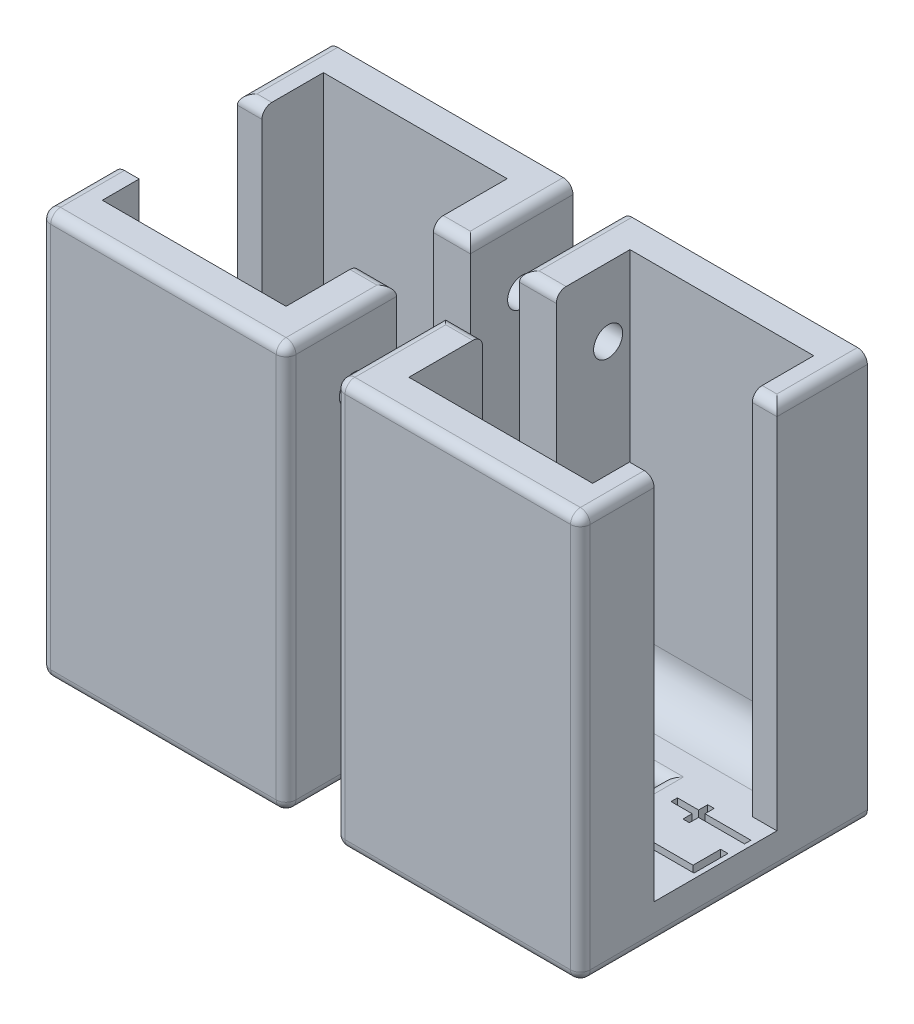
SolidWorks part; units mm, degrees
ref_plane "Front Plane" through (0, 0, 0) normal (0, 0, 1) x (1, 0, 0)
ref_plane "Top Plane" through (0, 0, 0) normal (0, 1, 0) x (1, 0, 0)
ref_plane "Right Plane" through (0, 0, 0) normal (1, 0, 0) x (0, 0, -1)
sketch "Sketch2" plane through (0, 0, 0) normal (0, 1, 0) x (1, 0, 0)
  line L0 (-9.5, -11.43) -> (9.5, -11.43)
  line L5 (12.04, -14.43) -> (-13.31, -14.43)
  line L10 (-13.31, -14.43) -> (-13.31, 15.24)
  line L15 (-13.31, 15.24) -> (12.04, 15.24)
  line L16 (12.04, 15.24) -> (12.04, 7.62)
  line L17 (12.04, -14.43) -> (12.04, -5.08)
  line L18 (12.04, 7.62) -> (9.5, 7.62)
  line L19 (9.5, 7.62) -> (9.5, 11.43)
  line L20 (9.5, 11.43) -> (-9.5, 11.43)
  line L21 (-9.5, 11.43) -> (-9.5, -11.43)
  line L22 (12.04, -5.08) -> (9.5, -5.08)
  line L24 (9.5, -11.43) -> (9.5, -5.08)
  point P6 (0, 11.43)
  point P12 (-9.5, 0)
  dimension "D1" = 22.86
  dimension "D2" = 19
  dimension "D3" = 3.81
  dimension "D4" = 3.81
  dimension "D5" = 7.62
  dimension "D6" = 2.54
  dimension "D7" = 5.08
  dimension "D8" = 3
extrude "Boss-Extrude2" add sketch "Sketch2" along normal blind 38.1
sketch "Sketch1" plane through (0, 0, 0) normal (0, 1, 0) x (1, 0, 0)
  line L1 (-13.31, -14.43) -> (12.04, -14.43)
  line L2 (-13.31, -14.43) -> (-13.31, 15.24)
  line L3 (-13.31, 15.24) -> (12.04, 15.24)
  line L4 (12.04, -14.43) -> (12.04, 15.24)
  point P0 (0, 0)
extrude "Boss-Extrude3" add sketch "Sketch1" against normal blind 3.81
sketch "Sketch3" plane through (0, 0, 0) normal (0, 1, 0) x (1, 0, 0)
  line L1 (-1.88, -3.81) -> (1.12, -3.81)
  line L2 (-1.88, -3.81) -> (-1.88, 3.81)
  line L3 (-1.88, 3.81) -> (1.12, 3.81)
  line L4 (1.12, -3.81) -> (1.12, 3.81)
  line L5 (-9.5, -11.43) -> (-9.5, 11.43) construction
  point P6 (-1.88, 0)
  dimension "D1" = 7.62
  dimension "D2" = 3
  dimension "D3" = 7.62
extrude "Cut-Extrude1" cut sketch "Sketch3" against normal through all
sketch "Sketch4" plane through (-9.5, 0, 0) normal (1, 0, 0) x (0, 0, -1)
  line L0 (-11.43, 38.1) -> (11.43, 38.1) construction
  line L1 (-3.81, 38.1) -> (3.81, 38.1)
  line L2 (-3.81, 38.1) -> (-3.81, 8)
  line L3 (-3.81, 8) -> (3.81, 8)
  line L4 (3.81, 38.1) -> (3.81, 8)
  line L5 (-11.43, 0) -> (11.43, 0) construction
  line L6 (-11.43, 38.1) -> (11.43, 38.1) construction
  point P10 (0, 38.1)
  point P11 (0, 38.1)
  dimension "D1" = 8
  dimension "D2" = 7.62
extrude "Cut-Extrude2" cut sketch "Sketch4" against normal through all
sketch "Sketch5" plane through (-9.5, 0, 0) normal (1, 0, 0) x (0, 0, -1)
  line L1 (-11.43, 0) -> (11.43, 0) construction
  circle A0 centre (-9.17, 31) radius 1.5
  circle A1 centre (8.23, 31) radius 1.5
  dimension "D3" = 3
  dimension "D1" = 2.26
  dimension "D2" = 17.4
  dimension "D4" = 31
extrude "Cut-Extrude3" cut sketch "Sketch5" against normal through all
sketch "Sketch6" plane through (0, 0, 14.43) normal (0, 0, 1) x (1, 0, 0)
  line L0 (-13.31, 38.1) -> (-13.31, -3.81) construction
  line L3 (-1.88, -3.81) -> (-1.88, 0) construction
  line L8 (12.04, 38.1) -> (12.04, 0) construction
  line L11 (-13.31, 38.1) -> (-9.5, 38.1) construction
  circle A0 centre (-11.405, 19.05) radius 1.45
  circle A1 centre (-3.81, -1.905) radius 1.45
  point P9 (-1.88, -1.905)
  point P20 (-11.405, 38.1)
  point P26 (12.04, 19.05)
  dimension "D1" = 2.9
  dimension "D2" = 9.5
extrude "Cut-Extrude4" cut sketch "Sketch6" against normal offset from surface (24.844 mm away) 6.604 up to face at (-11.405, 23.05, -3.81) offset beyond the face yes
fillet "Fillet1" radius 4 2 edges at (0, 0, -11.43) (0, 0, 11.43)
mirror "Mirror1" about plane through (0, 0, 0) normal (0, 0, 1) of bodies 106 120
delete or keep bodies "Body-Delete/Keep 1" type keep bodies bodies 116
fillet "Fillet4" radius 2.54 2 edges at (-11.405, 8, -3.81) (-11.405, 8, 3.81)
fillet "Fillet2" radius 1.016 11 edges at (-0.635, -3.81, 15.24) (-13.31, 17.145, 15.24) (-0.635, 38.1, 15.24) (12.04, 17.145, 15.24) (-13.31, -3.81, 0.405) (12.04, -3.81, 0.405) (12.04, 38.1, 11.43) (-13.31, 38.1, 9.525) (-13.31, 38.1, -9.12) (-11.405, 38.1, -3.81) (-11.405, 38.1, 3.81)
fillet "Fillet3" radius 1.27 4 edges at (-0.38, 0, -3.81) (-1.88, 0, 0) (-0.38, 0, 3.81) (1.12, 0, 0)
fillet "Fillet5" radius 1.016 2 edges at (10.77, 38.1, -5.08) (12.04, 38.1, -9.755)
ref_plane "Plane1" through (-15.85, 0, 0) normal (-1, 0, 0) x (0, 0, 1)
mirror "Mirror3" about plane through (-15.85, 0, 0) normal (-1, 0, 0) of bodies 116 117 121
sketch "Sketch7" plane through (0, 0, 0) normal (0, 1, 0) x (1, 0, 0)
  line L0 (11.5383, -3.9427) -> (11.5383, 17.9144) construction
  text T0 "Lt\r\n" font "Century Gothic" height in points 28
extrude "Cut-Extrude5" cut sketch "Sketch7" against normal blind 1.27
sketch "Sketch8" plane through (0, 0, 0) normal (0, 1, 0) x (1, 0, 0)
  line L0 (-42.724, -6.0799) -> (-42.724, 4.0801) construction
  line L1 (-42.724, -14.224) -> (-42.724, -7.62) construction
  text T0 "Rt\r\n" font "Century Gothic" height in points 28
  dimension "D1" = 10.16
extrude "Cut-Extrude6" cut sketch "Sketch8" against normal blind 1.27
equation "\".30.83in\"=0.83"
